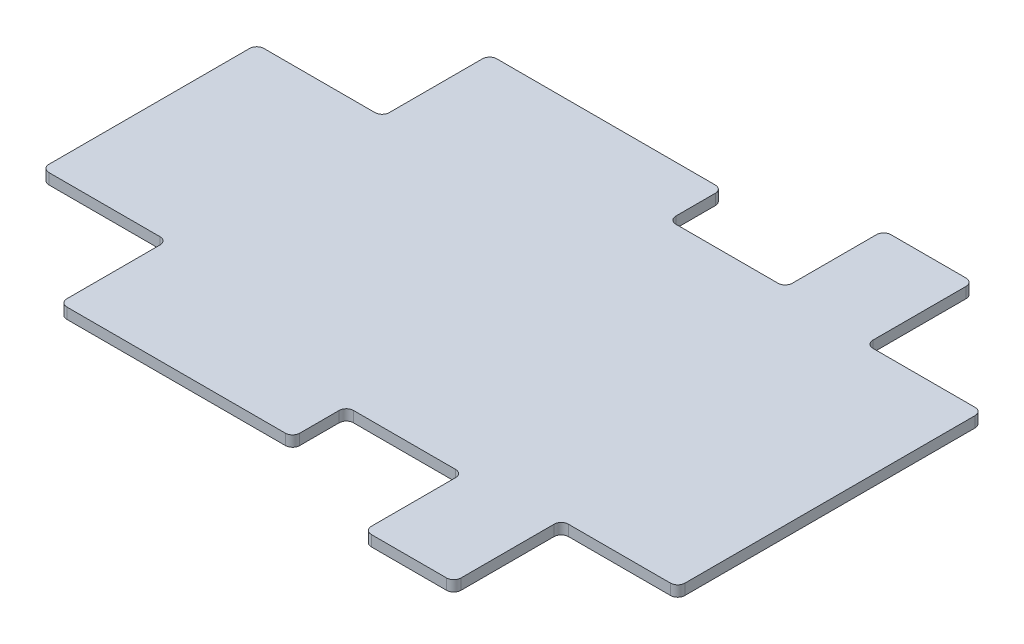
SolidWorks part; units mm, degrees
material "Aleación 1060"
ref_plane "Alzado" through (0, 0, 0) normal (0, 0, 1) x (1, 0, 0)
ref_plane "Planta" through (0, 0, 0) normal (0, 1, 0) x (1, 0, 0)
ref_plane "Vista lateral" through (0, 0, 0) normal (1, 0, 0) x (0, 0, -1)
sketch "Croquis1" plane through (0, 0, 0) normal (0, 1, 0) x (1, 0, 0)
  line L0 (0, 0) -> (-380, 0)
  line L1 (-380, 0) -> (-380, 60)
  line L2 (-380, 60) -> (-310, 60)
  line L3 (-310, 60) -> (-310, 120)
  line L4 (-310, 120) -> (-180, 120)
  line L5 (-180, 120) -> (-180, 90)
  line L6 (-180, 90) -> (-115, 90)
  line L7 (-115, 90) -> (-115, 145)
  line L8 (-115, 145) -> (-65, 145)
  line L9 (-65, 145) -> (-65, 85)
  line L10 (0, 0) -> (0, 85)
  line L11 (0, 85) -> (-65, 85)
  dimension "D1" = 380
  dimension "D2" = 60
  dimension "D3" = 70
  dimension "D4" = 120
  dimension "D5" = 130
  dimension "D6" = 30
  dimension "D7" = 50
  dimension "D8" = 85
  dimension "D9" = 65
  dimension "D10" = 60
extrude "Saliente-Extruir1" add sketch "Croquis1" along normal blind 6
mirror "Simetría1" about plane through (0, 6, 0) normal (0, 0, -1) of "Saliente-Extruir1"
fillet "Redondeo1" radius 4 20 edges at (-380, 3, -60) (-310, 3, -60) (-310, 3, -120) (-180, 3, -120) (-180, 3, -90) (-115, 3, -90) (-115, 3, -145) (-65, 3, -85) (-65, 3, -145) (0, 3, -85) (0, 3, 85) (-65, 3, 85) (-65, 3, 145) (-115, 3, 145) (-115, 3, 90) (-180, 3, 90) (-180, 3, 120) (-310, 3, 120) (-310, 3, 60) (-380, 3, 60)
sketch "Croquis2" plane through (0, 6, 0) normal (0, 1, 0) x (1, 0, 0)
  line L0 (-380, 0) -> (0, 0) construction
  line L1 (-380, 56) -> (-380, -56) construction
  line L2 (0, -81) -> (0, 81) construction
  line L3 (-214.7209, -131) -> (31.1095, -131) construction
  line L4 (-214.0485, -154) -> (44.3152, -154) construction
  line L5 (-69, -145) -> (-111, -145) construction
  line L6 (-34, -177) -> (-146, -177)
  line L7 (-34, -177) -> (-34, -131)
  line L8 (-34, -131) -> (-146, -131)
  line L9 (-146, -177) -> (-146, -131)
  line L10 (-34, -177) -> (-146, -131) construction
  line L11 (-34, -131) -> (-146, -177) construction
  line L13 (-364, -177) -> (-476, -177)
  line L14 (-364, -177) -> (-364, -131)
  line L15 (-364, -131) -> (-476, -131)
  line L16 (-476, -177) -> (-476, -131)
  line L17 (-364, -177) -> (-476, -131) construction
  line L18 (-364, -131) -> (-476, -177) construction
  line L19 (-34, 177) -> (-146, 177)
  line L20 (-34, 177) -> (-34, 131)
  line L21 (-34, 131) -> (-146, 131)
  line L22 (-146, 177) -> (-146, 131)
  line L23 (-364, 131) -> (-476, 177) construction
  line L24 (-364, 177) -> (-476, 131) construction
  line L25 (-476, 177) -> (-476, 131)
  line L26 (-364, 131) -> (-476, 131)
  line L27 (-364, 177) -> (-364, 131)
  line L28 (-364, 177) -> (-476, 177)
  point P10 (-90, -154)
  point P17 (-90, -145)
  point P18 (0, 0)
  point P20 (-420, -154)
  point P33 (-420, 154)
  dimension "D1" = 131
  dimension "D2" = 154
  dimension "D3" = 46
  dimension "D4" = 112
  dimension "D5" = 330
sketch "Croquis3" plane through (0, 6, 0) normal (0, 1, 0) x (1, 0, 0)
  line L0 (-90, -145) -> (-90, 145) construction
  line L1 (-69, -145) -> (-111, -145) construction
  line L2 (-69, 145) -> (-111, 145) construction
  line L3 (-151.9, 16.8885) -> (-151.9, -25.475) construction
  line L4 (-222.2, 27.5722) -> (-222.2, -25.475) construction
  dimension "D1" = 132.2
  dimension "D2" = 61.9
